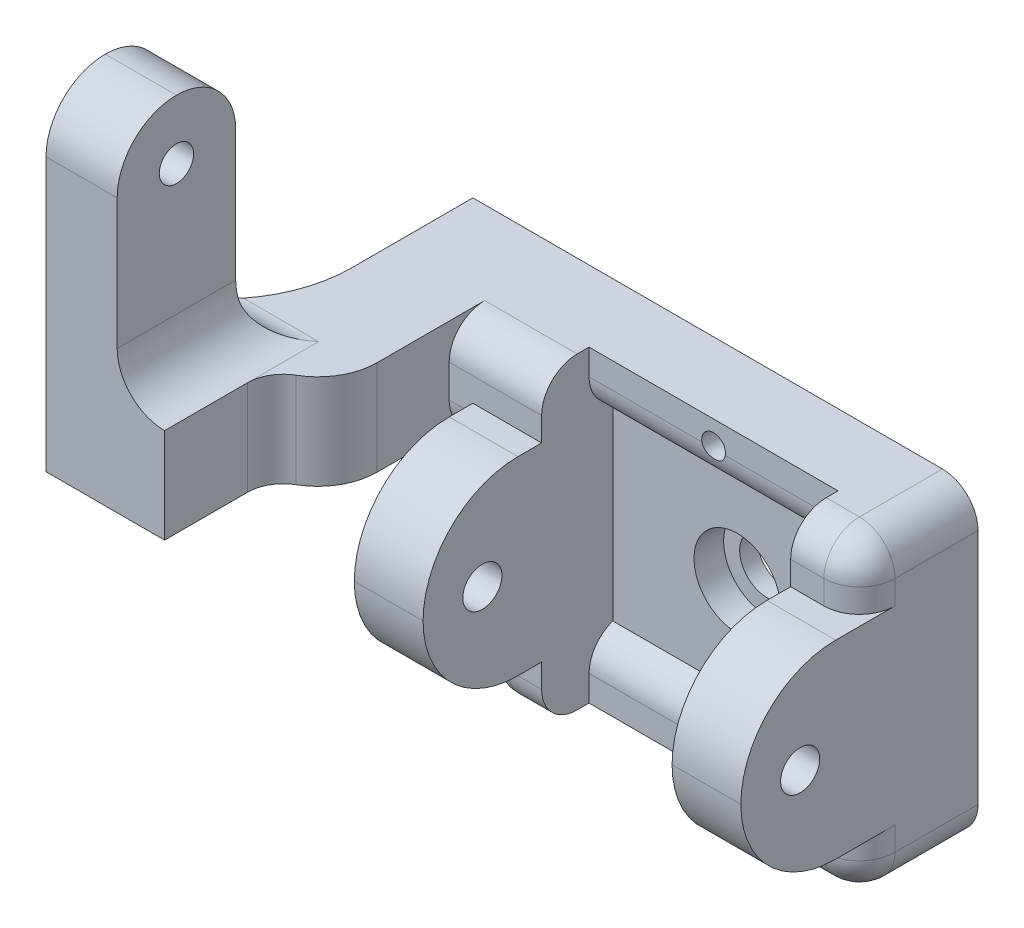
SolidWorks part; units mm, degrees
ref_plane "Front" through (0, 0, 0) normal (0, 0, 1) x (1, 0, 0)
ref_plane "Top" through (0, 0, 0) normal (0, 1, 0) x (1, 0, 0)
ref_plane "Right" through (0, 0, 0) normal (1, 0, 0) x (0, 0, -1)
sketch "Sketch1" plane through (0, 0, 0) normal (0, 0, 1) x (1, 0, 0)
  line L1 (0, 0) -> (-32.6, 0)
  line L2 (0, 0) -> (0, 26)
  line L3 (0, 26) -> (-32.6, 26)
  line L4 (-32.6, 0) -> (-32.6, 26)
  dimension "D1" = 32.6
  dimension "D2" = 26
extrude "Boss-Extrude1" add sketch "Sketch1" along normal blind 4
sketch "Sketch2" plane through (0, 0, 4) normal (0, 0, 1) x (1, 0, 0)
  line L0 (0, 26) -> (-32.6, 26) construction
  line L1 (0, 0) -> (0, 26) construction
  circle A0 centre (-16.3, 13) radius 3.65
  dimension "D1" = 7.3
  dimension "D2" = 13
  dimension "D3" = 16.3
extrude "Cut-Extrude1" cut sketch "Sketch2" against normal blind 2.5
sketch "Sketch3" plane through (0, 0, 1.5) normal (0, 0, 1) x (1, 0, 0)
  circle A0 centre (-16.3, 13) radius 2.3
  dimension "D1" = 4.6
extrude "Cut-Extrude2" cut sketch "Sketch3" against normal through all
sketch "Sketch4" plane through (0, 0, 4) normal (0, 0, 1) x (1, 0, 0)
  line L0 (-32.6, 0) -> (0, 0) construction
  line L1 (0, 26) -> (-5.8, 26)
  line L2 (0, 26) -> (0, 0)
  line L3 (0, 0) -> (-5.8, 0)
  line L4 (-5.8, 26) -> (-5.8, 0)
  line L6 (-32.6, 26) -> (-26.8, 26)
  line L7 (-32.6, 26) -> (-32.6, 0)
  line L8 (-32.6, 0) -> (-26.8, 0)
  line L9 (-26.8, 26) -> (-26.8, 0)
  dimension "D1" = 5.8
  dimension "D2" = 5.8
extrude "Boss-Extrude2" add sketch "Sketch4" along normal blind 16
sketch "Sketch5" plane through (0, 0, 0) normal (1, 0, 0) x (0, 0, -1)
  line L0 (-20, 0) -> (-20, 26) construction
  line L1 (-20, 0) -> (0, 0) construction
  circle A0 centre (-15, 13) radius 1.65
  dimension "D1" = 3.3
  dimension "D2" = 5
  dimension "D3" = 13
extrude "Cut-Extrude3" cut sketch "Sketch5" against normal through all
sketch "Sketch6" plane through (0, 0, 4) normal (0, 0, 1) x (1, 0, 0)
  line L1 (-26.8, 26) -> (-5.8, 26)
  line L2 (-26.8, 26) -> (-26.8, 21)
  line L3 (-26.8, 21) -> (-5.8, 21)
  line L4 (-5.8, 26) -> (-5.8, 21)
  line L5 (-26.8, 0) -> (-5.8, 0)
  line L6 (-26.8, 0) -> (-26.8, 5)
  line L7 (-26.8, 5) -> (-5.8, 5)
  line L8 (-5.8, 0) -> (-5.8, 5)
  dimension "D1" = 5
  dimension "D2" = 5
extrude "Boss-Extrude3" add sketch "Sketch6" along normal blind 2
sketch "Sketch7" plane through (-32.6, 0, 0) normal (-1, 0, 0) x (0, 0, 1)
  line L1 (20, 26) -> (10, 26)
  line L2 (20, 26) -> (20, 21)
  line L3 (20, 21) -> (10, 21)
  line L4 (10, 26) -> (10, 21)
  line L5 (20, 0) -> (10, 0)
  line L6 (20, 0) -> (20, 5)
  line L7 (20, 5) -> (10, 5)
  line L8 (10, 0) -> (10, 5)
  dimension "D1" = 10
  dimension "D2" = 10
  dimension "D3" = 5
  dimension "D4" = 5
extrude "Cut-Extrude4" cut sketch "Sketch7" against normal through all
fillet "Fillet1" radius 8 4 edges at (-2.9, 5, 20) (-2.9, 21, 20) (-29.7, 5, 20) (-29.7, 21, 20)
sketch "Sketch12" plane through (-32.6, 0, 0) normal (-1, 0, 0) x (0, 0, 1)
  line L0 (0, 26) -> (0, 0) construction
  line L1 (10, 26) -> (0, 26)
  line L2 (10, 26) -> (10, 18)
  line L3 (10, 18) -> (0, 18)
  line L4 (0, 26) -> (0, 18)
  dimension "D1" = 8
extrude "Boss-Extrude8" add sketch "Sketch12" along normal blind 10
sketch "Sketch13" plane through (0, 0, 10) normal (0, 0, 1) x (1, 0, 0)
  line L0 (-26.8, 26) -> (-42.6, 26) construction
  line L1 (-42.6, 18) -> (-34.6, 18)
  line L2 (-42.6, 18) -> (-42.6, 26)
  line L3 (-42.6, 26) -> (-34.6, 26)
  line L4 (-34.6, 18) -> (-34.6, 26)
  dimension "D1" = 8
extrude "Boss-Extrude9" add sketch "Sketch13" along normal blind 10
fillet "Fillet2" radius 3 4 edges at (-30.7, 26, 10) (-2.9, 26, 10) (-2.9, 0, 10) (-29.7, 0, 10)
sketch "Sketch14" plane through (0, 0, 20) normal (0, 0, 1) x (1, 0, 0)
  line L0 (-42.6, 18) -> (-34.6, 18) construction
  line L1 (-38.6, 18) -> (-48.6, 18)
  line L2 (-38.6, 18) -> (-38.6, 26)
  line L3 (-38.6, 26) -> (-48.6, 26)
  line L4 (-48.6, 18) -> (-48.6, 26)
  dimension "D1" = 8
  dimension "D2" = 10
extrude "Boss-Extrude10" add sketch "Sketch14" along normal blind 10
sketch "Sketch15" plane through (0, 26, 0) normal (0, 1, 0) x (1, 0, 0)
  line L1 (-48.6, -30) -> (-42.6, -30)
  line L2 (-48.6, -30) -> (-48.6, -20)
  line L3 (-48.6, -20) -> (-42.6, -20)
  line L4 (-42.6, -30) -> (-42.6, -20)
  dimension "D1" = 10
  dimension "D2" = 6
extrude "Boss-Extrude11" add sketch "Sketch15" along normal blind 20
fillet "Fillet10" radius 11 1 edges at (-42.6, 22, 20)
fillet "Fillet11" radius 3 1 edges at (-38.6, 22, 20)
fillet "Fillet12" radius 5 1 edges at (-34.6, 22, 20)
fillet "Fillet14" radius 4 1 edges at (-42.6, 26, 25)
fillet "Fillet15" radius 3 1 edges at (-43.6, 26, 20)
sketch "Sketch16" plane through (0, 0, 0) normal (0, 0, -1) x (-1, 0, 0)
  line L0 (42.6, 18) -> (32.6, 18)
  line L1 (32.6, 18) -> (32.6, 9)
  line L2 (32.6, 18) -> (32.6, 0) construction
  line L3 (32.6, 9) -> (42.6, 18)
  dimension "D1" = 9
extrude "Boss-Extrude12" add sketch "Sketch16" against normal blind 9
fillet "Fillet17" radius 3 1 edges at (-32.6, 9, 4.5)
fillet "Fillet18" radius 3 1 edges at (-33.6, 18, 10)
sketch "Sketch17" plane through (-48.6, 0, 0) normal (-1, 0, 0) x (0, 0, 1)
  line L0 (30, 46) -> (30, 18) construction
  line L1 (20, 46) -> (30, 46) construction
  circle A0 centre (25, 41) radius 1.45
  dimension "D2" = 5
  dimension "D1" = 2.9
  dimension "D3" = 5
extrude "Cut-Extrude5" cut sketch "Sketch17" against normal through all
fillet "Fillet19" radius 5 2 edges at (-45.6, 46, 20) (-45.6, 46, 30)
fillet "Fillet21" radius 3 2 edges at (-16.3, 21, 6) (-16.3, 5, 6)
fillet "Fillet22" radius 3 9 edges at (0, 22, 10) (0, 25.1213, 9.1213) (0, 4, 10) (0, 0.8787, 9.1213) (-32.6, 4, 10) (-32.6, 0.8787, 9.1213) (0, 26, 3.5) (0, 0, 3.5) (-32.6, 0, 3.5)
sketch "Sketch18" plane through (0, 0, 0) normal (0, 0, -1) x (-1, 0, 0)
  line L0 (29.6, 0) -> (3, 0) construction
  line L1 (3, 26) -> (42.6, 26) construction
  line L2 (0, 3) -> (0, 23) construction
  line L3 (32.6, 7.6639) -> (32.6, 3) construction
  circle A0 centre (16.3, 2) radius 1
  circle A1 centre (3.5, 13) radius 1.25
  circle A2 centre (29.1, 13) radius 1.25
  circle A3 centre (16.3, 24) radius 1
  dimension "D1" = 2
  dimension "D2" = 2
  dimension "D3" = 2.5
  dimension "D4" = 2.5
  dimension "D5" = 2
  dimension "D6" = 2
  dimension "D7" = 3.5
  dimension "D8" = 3.5
  dimension "D9" = 13
extrude "Cut-Extrude6" cut sketch "Sketch18" against normal blind 8
equation "\"滑动-垂直孔\" = 0.6"
equation "\"滑动-水平孔\"= 0.3"
equation "\"松动-垂直孔\" = 0.3"
equation "\"松动-水平孔\"= 0.1"
equation "\"正常-垂直孔\" = 0.15"
equation "\"正常-水平孔\"= 0"
equation "\"紧缩-垂直孔\"= 0"
equation "\"紧缩-水平孔\"= - 0.1"
equation "\"D4@Sketch18\"=\"紧缩-垂直孔\"+2.5"
equation "\"D3@Sketch18\"=\"紧缩-垂直孔\"+2.5"
equation "\"D2@Sketch18\"=\"紧缩-垂直孔\"+2"
equation "\"D1@Sketch18\"=\"紧缩-垂直孔\"+2"
equation "\"D1@Sketch3\"=\"滑动-垂直孔\"+4"
equation "\"D1@Sketch2\"=\"松动-垂直孔\"+7"
equation "\"D1@Sketch5\"=\"滑动-水平孔\"+3"
equation "\"D1@Sketch17\"=\"紧缩-水平孔\"+3"
